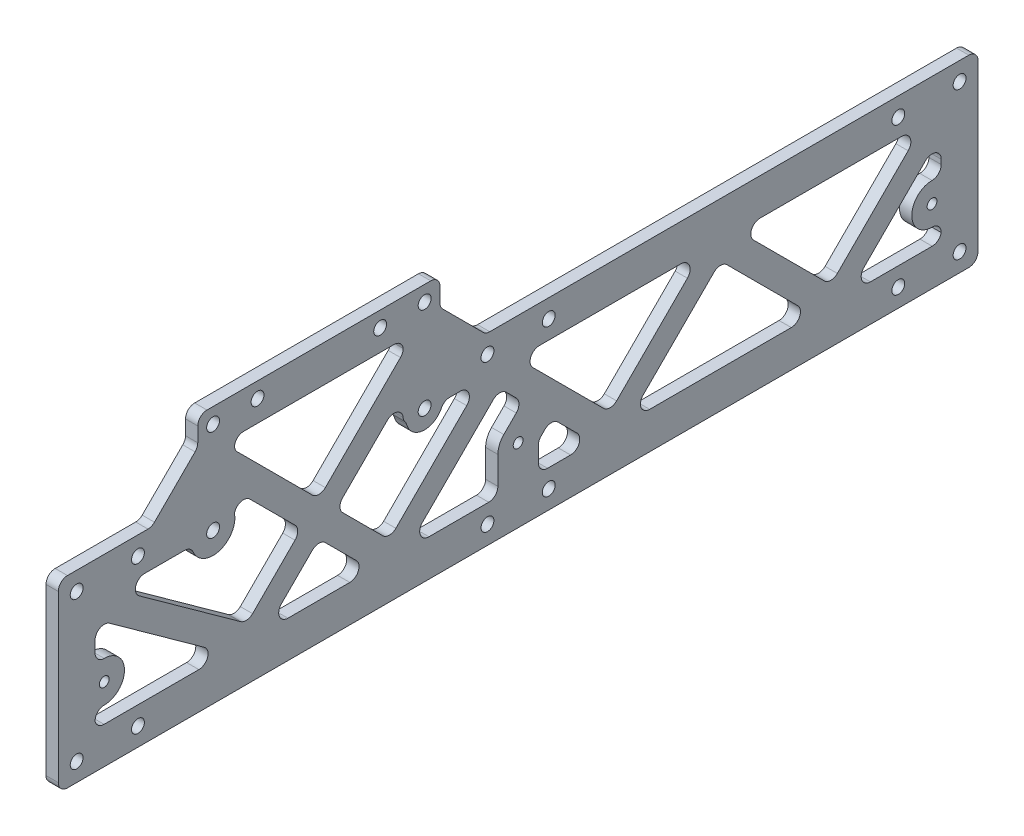
SolidWorks part; units mm, degrees
note: The reader was unsure of these and kept them because the rebuilt part matched: shared geometry of "草图2<4>".
material "Thornel Mat VMA"
ref_plane "前视基准面" through (0, 0, 0) normal (0, 0, 1) x (1, 0, 0)
ref_plane "上视基准面" through (0, 0, 0) normal (0, 1, 0) x (1, 0, 0)
ref_plane "右视基准面" through (0, 0, 0) normal (1, 0, 0) x (0, 0, -1)
other "Configuration Table"
sketch "草图1" plane through (0, 0, 0) normal (1, 0, 0) x (0, 0, -1)
  line L0 (135, 0) -> (135, 6) construction
  line L1 (135, 6) -> (285, 6) construction
  line L2 (285, 36) -> (-15, 36)
  line L3 (285, 36) -> (285, -24)
  line L4 (285, -24) -> (-15, -24)
  line L5 (-15, 36) -> (-15, -24)
  line L6 (285, 36) -> (-15, -24) construction
  line L7 (285, -24) -> (-15, 36) construction
  circle A0 centre (0, 0) radius 1.6
  circle A1 centre (135, 0) radius 1.6
  circle A2 centre (270, 0) radius 1.6
  circle A3 centre (-9, -18) radius 2.1
  circle A4 centre (11, -18) radius 2.1
  circle A5 centre (125, -18) radius 2.1
  circle A6 centre (145, -18) radius 2.1
  circle A7 centre (259, -18) radius 2.1
  circle A8 centre (279, -18) radius 2.1
  circle A9 centre (279, 30) radius 2.1
  circle A10 centre (259, 30) radius 2.1
  circle A11 centre (145, 30) radius 2.1
  circle A12 centre (125, 30) radius 2.1
  circle A13 centre (11, 30) radius 2.1
  circle A14 centre (-9, 30) radius 2.1
  dimension "D1" = 3.2
  dimension "D3" = 270
  dimension "D7" = 4.2
  dimension "D8" = 6
  dimension "D9" = 6
  dimension "D4" = 300
  dimension "D5" = 24
  dimension "D6" = 36
  dimension "D2" = 3
  dimension "D10" = 2
  dimension "D11" = 3
extrude "凸台-拉伸1" add sketch "草图1" along normal blind 4
sketch "草图2" plane through (0, 0, 0) normal (-1, 0, 0) x (0, 0, 1)
  line L1 (-285, 36) -> (15, 36) construction
  line L2 (-59.5, 40) -> (-70, 40) construction
  line L3 (-30.5, 36) -> (-30.5, 60)
  line L4 (-49.75, 29.75) -> (-90.25, 29.75) construction
  line L5 (-49.75, 29.75) -> (-49.75, 50.25) construction
  line L6 (-49.75, 50.25) -> (-90.25, 50.25) construction
  line L7 (-90.25, 29.75) -> (-90.25, 50.25) construction
  line L8 (-49.75, 29.75) -> (-90.25, 50.25) construction
  line L9 (-49.75, 50.25) -> (-90.25, 29.75) construction
  line L10 (-45.25, 35) -> (-94.75, 35) construction
  line L11 (-45.25, 35) -> (-45.25, 45) construction
  line L12 (-45.25, 45) -> (-94.75, 45) construction
  line L13 (-94.75, 35) -> (-94.75, 45) construction
  line L14 (-45.25, 35) -> (-94.75, 45) construction
  line L15 (-45.25, 45) -> (-94.75, 35) construction
  line L19 (-109.5, 60) -> (-109.5, 36)
  line L20 (-109.5, 36) -> (-30.5, 36)
  line L21 (-30.5, 60) -> (-109.5, 60)
  line L23 (-35.5, 25) -> (-104.5, 25) construction
  line L24 (-35.5, 25) -> (-35.5, 55) construction
  line L25 (-35.5, 55) -> (-104.5, 55) construction
  line L26 (-104.5, 25) -> (-104.5, 55) construction
  line L27 (-35.5, 25) -> (-104.5, 55) construction
  line L28 (-35.5, 55) -> (-104.5, 25) construction
  line L29 (15, 36) -> (15, -24) construction
  circle A0 centre (-59.5, 40) radius 20 construction
  circle A1 centre (-94.75, 45) radius 2.1 construction
  circle A2 centre (-94.75, 35) radius 2.1 construction
  circle A3 centre (-45.25, 45) radius 2.1 construction
  circle A4 centre (-45.25, 35) radius 2.1 construction
  circle A5 centre (-104.5, 55) radius 2.1
  circle A6 centre (-35.5, 55) radius 2.1
  circle A7 centre (-104.5, 25) radius 2.1
  circle A8 centre (-35.5, 25) radius 2.1
  line M20 (15, 36) -> (-285, 36)
  dimension "D1" = 40
  dimension "D2" = 85
  dimension "D3" = 4
  dimension "D9" = 4.2
  dimension "D12" = 4.2
  dimension "D4" = 10.5
  dimension "D5" = 20.5
  dimension "D6" = 40.5
  dimension "D7" = 10
  dimension "D8" = 49.5
  dimension "D10" = 24
  dimension "D11" = 5
  dimension "D13" = 5
  dimension "D14" = 5
  dimension "D15" = 79
extrude "凸台-拉伸2" add sketch "草图2" against normal blind 4 contours L3 L21 L19 A6 A5 M20
extrude "切除-拉伸1" cut sketch "草图2<4>" against normal blind 4 contours A7 | A8
sketch "草图2<4>" plane through (0, 0, 0) normal (-1, 0, 0) x (0, 0, 1) same geometry as "草图2"
sketch "草图3" plane through (0, 0, 0) normal (-1, 0, 0) x (0, 0, 1)
  line L0 (-97.5, 38.5) -> (-47, -12) construction
  line L1 (-47, -12) -> (3, 24) construction
  line L2 (-275.8284, 21.1716) -> (-237, -17.6569)
  line L3 (-237, -17.6569) -> (-201, 18.3431)
  line L4 (-201, 18.3431) -> (-165, -17.6569)
  line L5 (-165, -17.6569) -> (-129, 18.3431)
  line L6 (-129, 18.3431) -> (-93, -17.6569)
  line L7 (-93, -17.6569) -> (-39.6716, 35.6716)
  line L8 (-273, 24) -> (-237, -12) construction
  line L9 (-237, -12) -> (-201, 24) construction
  line L10 (-201, 24) -> (-165, -12) construction
  line L11 (-165, -12) -> (-129, 24) construction
  line L12 (-129, 24) -> (-93, -12) construction
  line L13 (-93, -12) -> (-42.5, 38.5) construction
  line L14 (-100.3284, 35.6716) -> (-47.4232, -17.2336)
  line L15 (-47.4232, -17.2336) -> (5.3372, 20.7539)
  line L16 (3, -12) -> (3, 24)
  line L17 (3, 24) -> (-42.5, 24)
  line L18 (-42.5, 24) -> (-42.5, 48)
  line L19 (-42.5, 48) -> (-97.5, 48)
  line L20 (-97.5, 48) -> (-97.5, 24)
  line L21 (-97.5, 24) -> (-273, 24)
  line L22 (-273, 24) -> (-273, -12)
  line L23 (-273, -12) -> (3, -12)
  line L24 (3, -12) -> (3, 24)
  line L25 (3, 24) -> (-42.5, 24)
  line L26 (-42.5, 24) -> (-42.5, 48)
  line L27 (-42.5, 48) -> (-97.5, 48)
  line L28 (-97.5, 48) -> (-97.5, 24)
  line L29 (-97.5, 24) -> (-273, 24)
  line L30 (-273, 24) -> (-273, -12)
  line L31 (-273, -12) -> (3, -12)
  line L32 (-270.1716, 26.8284) -> (-237, -6.3431)
  line L33 (-237, -6.3431) -> (-201, 29.6569)
  line L34 (-201, 29.6569) -> (-165, -6.3431)
  line L35 (-165, -6.3431) -> (-129, 29.6569)
  line L36 (-129, 29.6569) -> (-93, -6.3431)
  line L37 (-93, -6.3431) -> (-39.5584, 47.0985)
  line L38 (-98.2007, 44.8576) -> (-46.5768, -6.7664)
  line L39 (-46.5768, -6.7664) -> (0.6628, 27.2461)
  line L40 (-130.3331, 4.6669) -> (-136.5047, 10.8385)
  line L41 (-139.6669, -4.6669) -> (-145.8385, 1.5047)
  line L42 (-128.4, 0) -> (-128.4, -12)
  line L43 (-141.6, 0) -> (-141.6, -12)
  line L44 (-94.6716, 41.3284) -> (-46.5768, -6.7664) construction
  line L45 (-93, -6.3431) -> (-45.3284, 41.3284) construction
  circle A2 centre (-104.5, 25) radius 6.1
  circle A3 centre (-104.5, 25) radius 6.1
  circle A5 centre (-270, 0) radius 6.6
  circle A6 centre (-270, 0) radius 6.6
  circle A8 centre (-35.5, 25) radius 7.1
  circle A9 centre (-35.5, 25) radius 7.1
  circle A11 centre (0, 0) radius 6.6
  circle A12 centre (0, 0) radius 6.6
  circle A14 centre (-135, 0) radius 6.6
  circle A15 centre (-135, 0) radius 6.6
  dimension "D7" = 276
  dimension "D8" = 45
  dimension "D9" = 4
  dimension "D1" = 12
  dimension "D2" = 4
  dimension "D3" = 5
  dimension "D4" = 5
  dimension "D5" = 5
  dimension "D6" = 5
  dimension "D10" = 4
extrude "切除-拉伸2" cut sketch "草图3" against normal blind 10
fillet "圆角1" radius 3 5 edges at (2, -6.7664, -46.5768) (2, -5.8788, 3) (2, 24, -206.6569) (2, 19.0711, 3) (2, 26.1874, -42.5)
fillet "圆角2" radius 3 6 edges at (2, -12, 3) (2, 44.1569, -42.5) (2, 18.3431, -273) (2, -12, -40.1543) (2, 5.8788, -273) (2, 44.1569, -97.5)
fillet "圆角3" radius 3 5 edges at (2, 48, -42.5) (2, 11, -75.6569) (2, -12, -242.6569) (2, 32.8431, -97.5) (2, 48, -97.5)
fillet "圆角4" radius 3 13 edges at (2, 24, -97.5) (2, 11, -64.3431) (2, -6.3431, -165) (2, 32.8431, -42.5) (2, 18.3431, -201) (2, 10.8385, -136.5047) (2, -12, -128.4) (2, -5.8788, -273) (2, 24, -110.5175) (2, 16.6569, -70) (2, -6.3431, -93) (2, 24, -123.3431) (2, 24, -267.3431)
fillet "圆角5" radius 3 19 edges at (2, -12, -273) (2, 24, -195.3431) (2, -6.3431, -237) (2, -12, -52.6569) (2, 24, -134.6569) (2, -2.7338, -141.6) (2, 24, -3.8457) (2, -12, -159.3431) (2, 5.3431, -70) (2, 24, -28.4708) (2, 5.8788, 3) (2, -12, -141.6) (2, 1.5047, -145.8385) (2, -12, -87.3431) (2, -12, -231.3431) (2, 24, -98.4825) (2, -12, -98.6569) (2, -12, -170.6569) (2, 18.3431, -129)
chamfer "倒角1" distance 15 angle 45 2 edges at (2, 36, -30.5) (2, 36, -109.5)
fillet "圆角6" radius 3 10 edges at (2, 36, 15) (2, 36, -15.5) (2, 51, -30.5) (2, 60, -30.5) (2, 51, -109.5) (2, 36, -124.5) (2, 36, -285) (2, -24, -285) (2, -24, 15) (2, 60, -109.5)
sketch "草图4" plane through (0, 0, 0) normal (-1, 0, 0) x (0, 0, 1)
  line L0 (-104.5, 55) -> (-35.5, 55) construction
  circle A0 centre (-90, 55) radius 2.1
  circle A1 centre (-50, 55) radius 2.1
  point P6 (-70, 55)
  dimension "D1" = 4.2
  dimension "D2" = 20
  dimension "D3" = 2
extrude "切除-拉伸3" cut sketch "草图4" against normal blind 10
